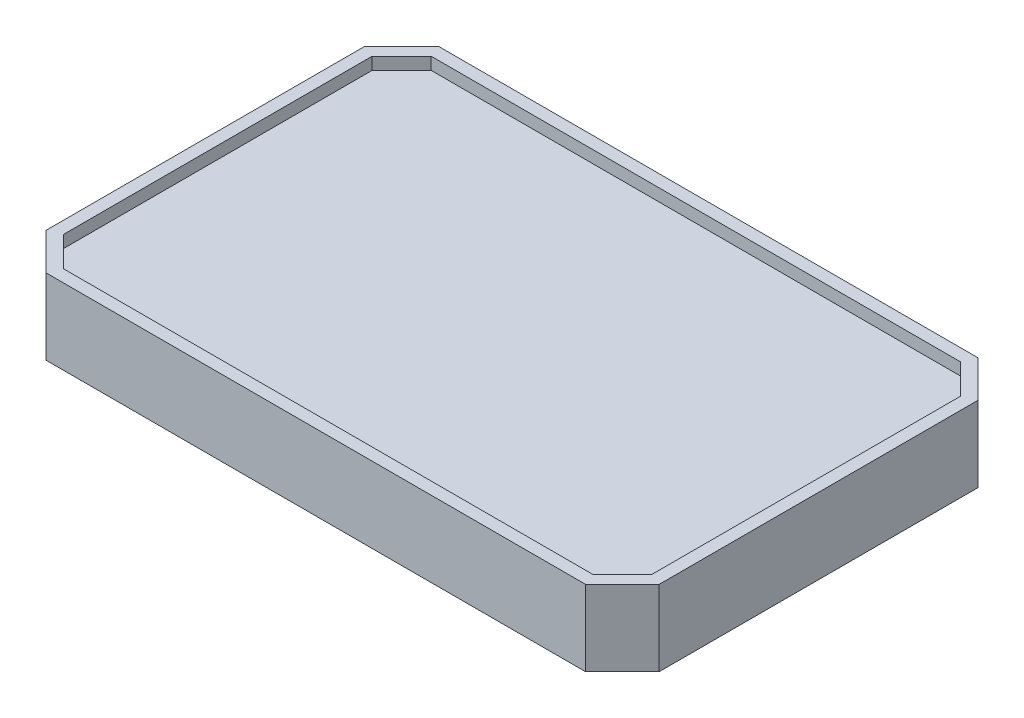
SolidWorks part; units mm, degrees
ref_plane "Plano frontal" through (0, 0, 0) normal (0, 0, 1) x (1, 0, 0)
ref_plane "Plano superior" through (0, 0, 0) normal (0, 1, 0) x (1, 0, 0)
ref_plane "Plano direito" through (0, 0, 0) normal (1, 0, 0) x (0, 0, -1)
sketch "Esboço1" plane through (0, 0, 0) normal (0, 1, 0) x (1, 0, 0)
  line L0 (2.5, 1.6) -> (-2.5, -1.6) construction
  line L1 (-2.5, 1.6) -> (2.5, 1.6)
  line L2 (-2.5, 1.6) -> (-2.5, -1.6)
  line L3 (-2.5, -1.6) -> (2.5, -1.6)
  line L4 (2.5, 1.6) -> (2.5, -1.6)
  dimension "D1" = 5
  dimension "D2" = 3.2
extrude "Extrusão1" add sketch "Esboço1" along normal blind 0.617
chamfer "Chanfro3" distance 0.3 angle 45 1 edges at (2.5, 0.3085, 1.6)
chamfer "Chanfro4" distance 0.3 angle 45 1 edges at (-2.5, 0.3085, 1.6)
chamfer "Chanfro5" distance 0.3 angle 45 1 edges at (2.5, 0.3085, -1.6)
chamfer "Chanfro6" distance 0.3 angle 45 1 edges at (-2.5, 0.3085, -1.6)
sketch "Esboço4" plane through (0, 0, 0) normal (0, 1, 0) x (1, 0, 0)
  line L0 (1.25, 0.75) -> (1.25, 1.55)
  line L1 (1.25, 1.55) -> (2.1793, 1.55)
  line L2 (2.1793, 1.55) -> (2.45, 1.2793)
  line L3 (2.45, 1.2793) -> (2.45, 0.75)
  line L4 (2.45, 0.75) -> (1.25, 0.75)
  line L6 (2.2, 1.6) -> (-2.2, 1.6) construction
  line L7 (2.5, -1.3) -> (2.5, 1.3) construction
  line L10 (2.2, 1.6) -> (2.5, 1.3) construction
  dimension "D1" = 1.2
  dimension "D2" = 0.8
  dimension "D3" = 0.05
  dimension "D4" = 0.05
  dimension "D5" = 0.05
extrude "Extrusão6" cut sketch "Esboço4" along normal blind 0.1
sketch "Esboço6" plane through (0, 0, 0) normal (0, 1, 0) x (1, 0, 0)
  line L0 (1.25, -1.55) -> (1.25, -0.75)
  line L1 (1.25, -0.75) -> (2.45, -0.75)
  line L2 (2.45, -0.75) -> (2.45, -1.2793)
  line L3 (2.45, -1.2793) -> (2.1793, -1.55)
  line L4 (2.1793, -1.55) -> (1.25, -1.55)
  line L6 (-2.2, -1.6) -> (2.2, -1.6) construction
  line L8 (2.5, -1.3) -> (2.5, 1.3) construction
  line L9 (2.5, -1.3) -> (2.2, -1.6) construction
  dimension "D1" = 1.2
  dimension "D2" = 0.8
  dimension "D3" = 0.05
  dimension "D4" = 0.05
  dimension "D5" = 0.05
extrude "Extrusão8" cut sketch "Esboço6" along normal blind 0.1
sketch "Esboço7" plane through (0, 0, 0) normal (0, 1, 0) x (1, 0, 0)
  line L0 (-2.45, -0.75) -> (-1.5187, -0.75)
  line L1 (-1.5187, -0.75) -> (-1.25, -1.0187)
  line L2 (-1.25, -1.0187) -> (-1.25, -1.55)
  line L3 (-1.25, -1.55) -> (-2.1793, -1.55)
  line L4 (-2.1793, -1.55) -> (-2.45, -1.2793)
  line L5 (-2.45, -1.2793) -> (-2.45, -0.75)
  line L6 (-2.2, -1.6) -> (2.2, -1.6) construction
  line L7 (-2.5, 1.3) -> (-2.5, -1.3) construction
  line L8 (-2.2, -1.6) -> (-2.5, -1.3) construction
  dimension "D1" = 0.05
  dimension "D2" = 0.05
  dimension "D3" = 0.05
  dimension "D4" = 1.2
  dimension "D5" = 0.8
  dimension "D6" = 0.38
extrude "Extrusão9" cut sketch "Esboço7" along normal blind 0.1
sketch "Esboço10" plane through (0, 0.617, 0) normal (0, 1, 0) x (1, 0, 0)
  line L0 (-2.4, 1.2586) -> (-2.1586, 1.5)
  line L1 (-2.1586, 1.5) -> (2.1586, 1.5)
  line L2 (2.1586, 1.5) -> (2.4, 1.2586)
  line L3 (2.4, 1.2586) -> (2.4, -1.2586)
  line L4 (2.4, -1.2586) -> (2.1586, -1.5)
  line L5 (2.1586, -1.5) -> (-2.1586, -1.5)
  line L6 (-2.1586, -1.5) -> (-2.4, -1.2586)
  line L7 (-2.4, -1.2586) -> (-2.4, 1.2586)
  line L8 (-2.2, -1.6) -> (2.2, -1.6) construction
  line L9 (2.2, 1.6) -> (-2.2, 1.6) construction
  line L10 (-2.5, 1.3) -> (-2.5, -1.3) construction
  line L11 (2.5, -1.3) -> (2.5, 1.3) construction
  line L12 (-2.2, 1.6) -> (-2.5, 1.3) construction
  line L13 (2.5, 1.3) -> (2.2, 1.6) construction
  line L14 (2.2, -1.6) -> (2.5, -1.3) construction
  line L15 (-2.5, -1.3) -> (-2.2, -1.6) construction
  dimension "D1" = 0.1
  dimension "D2" = 0.1
  dimension "D3" = 0.1
  dimension "D4" = 0.1
  dimension "D5" = 0.1
  dimension "D6" = 0.1
  dimension "D7" = 0.1
  dimension "D8" = 0.1
extrude "Extrusão13" cut sketch "Esboço10" against normal blind 0.1
sketch "Esboço11" plane through (0, 0, 0) normal (0, 1, 0) x (1, 0, 0)
  line L0 (-2.45, 1.2793) -> (-2.45, 0.75)
  line L1 (-2.45, 0.75) -> (-1.25, 0.75)
  line L2 (-1.25, 0.75) -> (-1.25, 1.55)
  line L3 (-1.25, 1.55) -> (-2.1793, 1.55)
  line L4 (-2.1793, 1.55) -> (-2.45, 1.2793)
  line L5 (-2.5, 1.3) -> (-2.2, 1.6) construction
  line L6 (2.2, 1.6) -> (-2.2, 1.6) construction
  line L7 (-2.5, 1.3) -> (-2.5, -1.3) construction
  dimension "D1" = 1.2
  dimension "D2" = 0.8
  dimension "D3" = 0.05
  dimension "D4" = 0.05
  dimension "D5" = 0.05
extrude "Extrusão14" cut sketch "Esboço11" along normal blind 0.1
